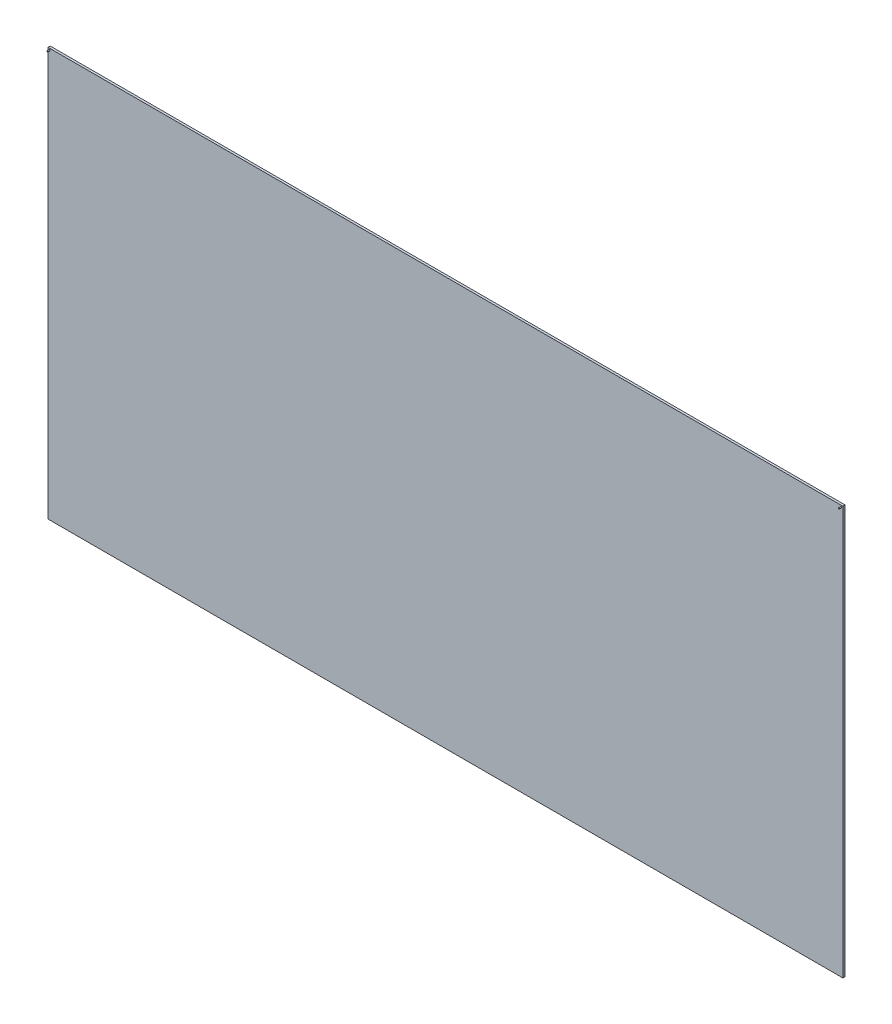
SolidWorks part; units mm, degrees
ref_plane "Front Plane" through (0, 0, 0) normal (0, 0, 1) x (1, 0, 0)
ref_plane "Top Plane" through (0, 0, 0) normal (0, 1, 0) x (1, 0, 0)
ref_plane "Right Plane" through (0, 0, 0) normal (1, 0, 0) x (0, 0, -1)
sketch "Sketch1" plane through (0, 0, 0) normal (0, 0, 1) x (1, 0, 0)
  line L0 (0, 1767.767) -> (3535.53, 0) construction
  line L1 (0, 0) -> (3535.53, 0) construction
  line L2 (0, 0) -> (0, 1767.767) construction
  line L3 (0, 1767.767) -> (3535.53, 1767.767) construction
  line L4 (3535.53, 0) -> (3535.53, 1767.767) construction
  line L5 (3535.53, 1767.767) -> (0, 0) construction
  line L7 (-15, 1782.767) -> (3550.53, 1782.767)
  line L8 (-15, 1782.767) -> (-15, -50)
  line L9 (-15, -50) -> (3550.53, -50)
  line L10 (3550.53, 1782.767) -> (3550.53, -50)
  dimension "D1" = 1767.767
  dimension "D2" = 3535.53
  dimension "D3" = 15
  dimension "D4" = 15
  dimension "D5" = 15
  dimension "D6" = 50
extrude "Boss-Extrude1" add sketch "Sketch1" along normal blind 10
sketch "Sketch2" plane through (0, 0, 10) normal (0, 0, 1) x (1, 0, 0)
  line L0 (0, 1767.767) -> (-15, 1782.767) construction
  line L1 (1767.765, 1782.767) -> (1767.765, -50) construction
  line L2 (-15, 1782.767) -> (3550.53, 1782.767) construction
  line L3 (-15, -50) -> (3550.53, -50) construction
  line L4 (3535.53, 1767.767) -> (3550.53, 1782.767) construction
  circle A0 centre (-7.5, 1775.267) radius 2.5
  circle A1 centre (3543.03, 1775.267) radius 2.5
  dimension "D1" = 5
extrude "Boss-Extrude2" add sketch "Sketch2" along normal blind 10
sketch "Sketch3" plane through (0, 0, 10) normal (0, 0, 1) x (1, 0, 0)
  line L1 (0, 1767.767) -> (3535.53, 1767.767) construction
  line L2 (0, 1767.767) -> (0, 0) construction
  line L3 (0, 0) -> (3535.53, 0) construction
  line L4 (3535.53, 1767.767) -> (3535.53, 0) construction
